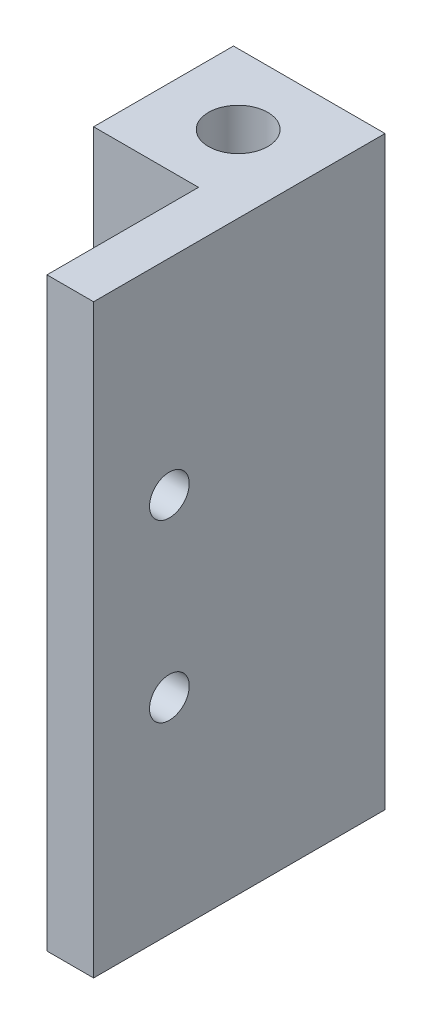
SolidWorks part; units mm, degrees
material "PET"
ref_plane "Front" through (0, 0, 0) normal (0, 0, 1) x (1, 0, 0)
ref_plane "Top" through (0, 0, 0) normal (0, 1, 0) x (1, 0, 0)
ref_plane "Right" through (0, 0, 0) normal (1, 0, 0) x (0, 0, -1)
sketch "Sketch1" plane through (0, 0, 0) normal (0, 1, 0) x (1, 0, 0)
  line L0 (0, 0) -> (-7.1438, 0)
  line L1 (-7.1438, 0) -> (-7.1438, 9.525)
  line L2 (-7.1438, 9.525) -> (3.175, 9.525)
  line L3 (3.175, 9.525) -> (3.175, -10.3187)
  line L4 (3.175, -10.3187) -> (0, -10.3187)
  line L5 (0, -10.3187) -> (0, 0)
  dimension "D2" = 9.525
  dimension "D3" = 19.8438
  dimension "D4" = 3.175
  dimension "D6" = 10.3187
extrude "Boss-Extrude1" add sketch "Sketch1" along normal blind 39.878
sketch "Sketch6" plane through (0, 39.878, 0) normal (0, 1, 0) x (1, 0, 0)
  line L16 (3.175, 9.525) -> (-7.1438, 9.525) construction
  line L17 (-7.1438, 9.525) -> (-7.1438, 0) construction
  point P0 (-2.0638, 4.7625)
  dimension "D1" = 4.7625
  dimension "D2" = 5.08
hole_wizard "#10-32 Tapped Hole1" positions "Sketch6" profile "Sketch5" tap size "#10-32" standard "ANSI Inch" end condition up to next
sketch "Sketch5" plane through (-2.0638, 39.878, -4.7625) normal (1, 0, 0) x (0, 0, 1)
  line L0 (0, 0) -> (0, 39.878)
  line L1 (0, 39.878) -> (2.0193, 39.878)
  line L2 (2.0193, 39.878) -> (2.0193, 0)
  line L5 (2.0193, 0) -> (0, 0)
  line L11 (0, -6.35) -> (0, 107.95) construction
  dimension "Thru Tap Drill Dia." = 4.0386
  dimension "Thru Tap Drill Depth" = 39.878
cosmetic thread "Hole Thread1" parameters "D2"=4.826
sketch "Sketch9" plane through (0, 0, 0) normal (-1, 0, 0) x (0, 0, 1)
  line L0 (0, 39.878) -> (10.3187, 39.878) construction
  line L1 (0, 25.9055) -> (5.1594, 25.9055) construction
  line L2 (0, 39.878) -> (0, 0) construction
  line L3 (5.1594, 25.9055) -> (10.3188, 25.9055) construction
  line L4 (10.3187, 39.878) -> (10.3187, 0) construction
  line L5 (0, 0) -> (10.3187, 0) construction
  point P0 (5.1594, 25.9055)
  point P19 (5.1594, 13.9725)
  dimension "D1" = 13.9725
  dimension "D2" = 13.9725
hole_wizard "#6-32 Tapped Hole1" positions "Sketch9" profile "Sketch8" tap size "#6-32" standard "ANSI Inch" end condition up to next
sketch "Sketch8" plane through (0, 25.9055, 5.1594) normal (0, 1, 0) x (0, 0, 1)
  line L0 (0, 0) -> (0, 3.175)
  line L1 (0, 3.175) -> (1.3525, 3.175)
  line L2 (1.3525, 3.175) -> (1.3525, 0)
  line L5 (1.3525, 0) -> (0, 0)
  line L11 (0, -6.35) -> (0, 107.95) construction
  dimension "Thru Tap Drill Dia." = 2.7051
  dimension "Thru Tap Drill Depth" = 3.175
cosmetic thread "Hole Thread2" parameters "D2"=3.5052
cosmetic thread "Hole Thread3" parameters "D2"=3.5052
